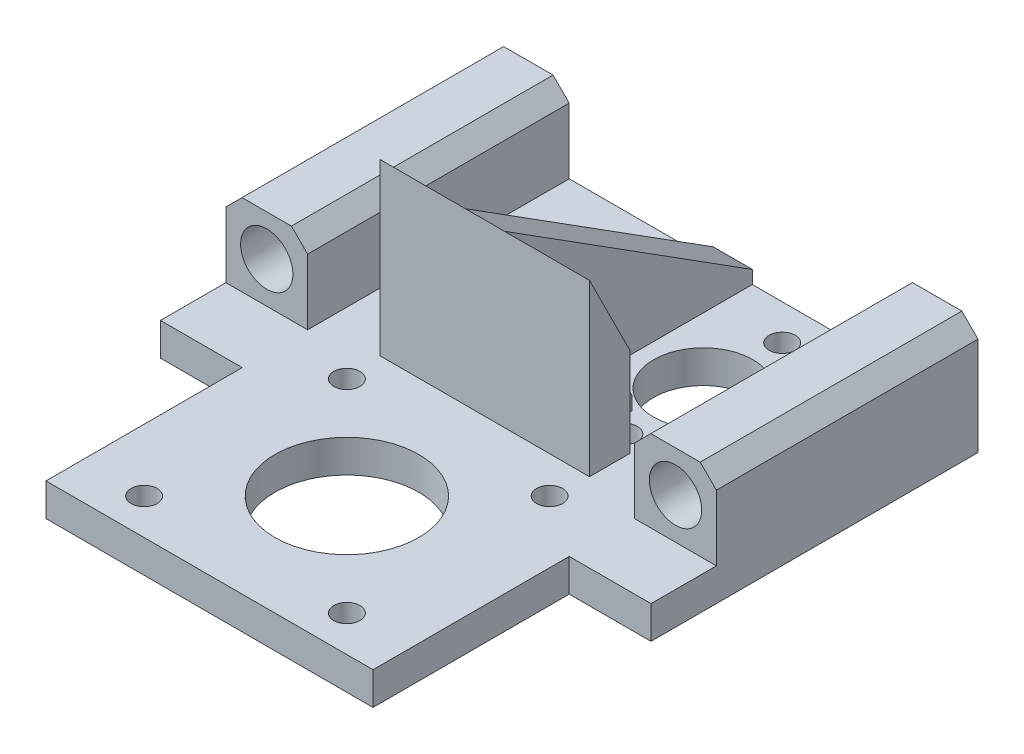
SolidWorks part; units mm, degrees
ref_plane "Front Plane" through (0, 0, 0) normal (0, 0, 1) x (1, 0, 0)
ref_plane "Top Plane" through (0, 0, 0) normal (0, 1, 0) x (1, 0, 0)
ref_plane "Right Plane" through (0, 0, 0) normal (1, 0, 0) x (0, 0, -1)
sketch "Sketch1" plane through (0, 0, 0) normal (0, 1, 0) x (1, 0, 0)
  line L0 (0, 32.5) -> (75, 32.5) construction
  line L1 (0, 0) -> (75, 0)
  line L2 (0, 0) -> (0, 50)
  line L3 (0, 50) -> (75, 50)
  line L4 (75, 0) -> (75, 50)
  line L5 (37.5, 50) -> (37.5, 0) construction
  line L6 (37.5, 32.5) -> (24.5, 32.5) construction
  line L7 (37.5, 32.5) -> (50.5, 32.5) construction
  circle A0 centre (24.5, 32.5) radius 5.1
  circle A1 centre (50.5, 32.5) radius 7.6
  point P15 (37.5, 32.5)
  dimension "D2" = 10.2
  dimension "D6" = 15.2
  dimension "D1" = 26
  dimension "D3" = 75
  dimension "D4" = 50
  dimension "D5" = 17.5
extrude "Boss-Extrude1" add sketch "Sketch1" along normal blind 5
sketch "Sketch2" plane through (0, 5, 0) normal (0, 1, 0) x (1, 0, 0)
  line L4 (0, 50) -> (12.5, 50)
  line L5 (0, 50) -> (0, 10)
  line L6 (0, 10) -> (12.5, 10)
  line L7 (12.5, 50) -> (12.5, 10)
  line L8 (75, 50) -> (62.5, 50)
  line L9 (75, 50) -> (75, 10)
  line L10 (75, 10) -> (62.5, 10)
  line L11 (62.5, 50) -> (62.5, 10)
  dimension "D1" = 40
  dimension "D3" = 12.5
extrude "Boss-Extrude2" add sketch "Sketch2" along normal blind 12.5
sketch "Sketch3" plane through (0, 0, -50) normal (0, 0, -1) x (-1, 0, 0)
  line L0 (-37.5, 0) -> (-37.5, 50000) construction
  line L1 (-75, 0) -> (0, 0) construction
  line L2 (-62.5, 5) -> (-12.5, 5) construction
  line L3 (-72.5251, 17.5) -> (-75, 17.5)
  line L4 (-75, 17.5) -> (-62.5, 17.5) construction
  line L5 (-75, 17.5) -> (-75, 15.0251)
  line L6 (-75, 17.5) -> (-75, 0) construction
  line L7 (-75, 15.0251) -> (-72.5251, 17.5)
  line L8 (-62.5, 17.5) -> (-64.9749, 17.5)
  line L9 (-64.9749, 17.5) -> (-62.5, 15.0251)
  line L10 (-62.5, 17.5) -> (-62.5, 5) construction
  line L11 (-62.5, 15.0251) -> (-62.5, 17.5)
  line L12 (-68.75, 17.5) -> (-68.75, 0) construction
  line L13 (-62.5, 11.25) -> (-75, 11.25) construction
  line L14 (-12.5, 11.25) -> (0, 11.25) construction
  line L15 (-6.25, 17.5) -> (-6.25, 0) construction
  line L16 (-12.5, 15.0251) -> (-12.5, 17.5)
  line L17 (-10.0251, 17.5) -> (-12.5, 15.0251)
  line L18 (-12.5, 17.5) -> (-10.0251, 17.5)
  line L19 (0, 15.0251) -> (-2.4749, 17.5)
  line L20 (0, 17.5) -> (0, 15.0251)
  line L21 (-2.4749, 17.5) -> (0, 17.5)
  circle A0 centre (-68.75, 11.25) radius 4
  circle A1 centre (-6.25, 11.25) radius 4
  point P4 (-37.5, 0)
  point P7 (-37.5, 5)
  dimension "D1" = 8
  dimension "D2" = 3.5
extrude "Cut-Extrude1" cut sketch "Sketch3" against normal through all
sketch "Sketch4" plane through (0, 5, 0) normal (0, 1, 0) x (1, 0, 0)
  line L0 (0, 0) -> (75, 0) construction
  line L1 (62.5, 0) -> (12.5, 0)
  line L2 (62.5, 0) -> (62.5, -30)
  line L3 (62.5, -30) -> (12.5, -30)
  line L4 (12.5, 0) -> (12.5, -30)
  line L5 (37.5, 50) -> (37.5, 0) construction
  line L6 (62.5, 50) -> (12.5, 50) construction
  point P10 (37.5, 0)
  dimension "D1" = 50
  dimension "D2" = 30
extrude "Boss-Extrude3" add sketch "Sketch4" against normal up to surface (5 mm away) up to face at (24.5, 0, -27.4)
sketch "Sketch5" plane through (0, 5, 0) normal (0, 1, 0) x (1, 0, 0)
  line L0 (37.5, -30) -> (37.5, 50) construction
  line L1 (12.5, -30) -> (62.5, -30) construction
  line L2 (62.5, 50) -> (12.5, 50) construction
  line L3 (58.5, -9) -> (16.5, -9) construction
  circle A0 centre (22, -24.5) radius 2
  circle A1 centre (22, 6.5) radius 2
  circle A2 centre (53, 6.5) radius 2
  circle A3 centre (53, -24.5) radius 2
  circle A4 centre (37.5, -9) radius 11
  point P8 (37.5, -9)
  dimension "D5" = 4
  dimension "D6" = 22
  dimension "D1" = 42
  dimension "D2" = 21
  dimension "D3" = 15.5
  dimension "D4" = 15.5
extrude "Cut-Extrude2" cut sketch "Sketch5" against normal through all
sketch "Sketch6" plane through (0, 5, 0) normal (0, 1, 0) x (1, 0, 0)
  line L0 (37.5, -30) -> (37.5, 12.1) construction
  line L1 (12.5, -30) -> (62.5, -30) construction
  line L3 (53.5, 12.1) -> (21.5, 12.1)
  line L4 (53.5, 12.1) -> (53.5, 24.1)
  line L5 (53.5, 24.1) -> (21.5, 24.1)
  line L6 (21.5, 12.1) -> (21.5, 24.1)
  point P9 (37.5, 12.1)
  dimension "D1" = 42.1
  dimension "D2" = 12
  dimension "D3" = 32
extrude "Boss-Extrude4" add sketch "Sketch6" along normal blind 2
sketch "Sketch8" plane through (53.5, 0, 0) normal (1, 0, 0) x (0, 0, -1)
  line L0 (24.1, 7) -> (12.1, 7)
  line L1 (12.1, 7) -> (12.1, 31)
  line L2 (12.1, 31) -> (24.1, 7)
  dimension "D1" = 24
extrude "Boss-Extrude6" add sketch "Sketch8" against normal up to surface (32 mm away) up to face at (21.5, 6, -18.1)
sketch "Sketch9" plane through (0, 5, 0) normal (0, 1, 0) x (1, 0, 0)
  line L0 (62.5, 50) -> (12.5, 50) construction
  line L1 (40.5, 50) -> (34.5, 50)
  line L2 (40.5, 50) -> (40.5, 24.1)
  line L3 (40.5, 24.1) -> (34.5, 24.1)
  line L4 (34.5, 50) -> (34.5, 24.1)
  line L5 (53.5, 24.1) -> (21.5, 24.1) construction
  line L6 (37.5, 50) -> (37.5, -138.6407) construction
  point P10 (37.5, 50)
  point P11 (37.5, 50)
  dimension "D1" = 6
extrude "Boss-Extrude7" add sketch "Sketch9" along normal up to vertex (2 mm away) up to point (21.5, 7, -24.1)
sketch "Sketch10" plane through (34.5, 0, 0) normal (-1, 0, 0) x (0, 0, 1)
  line L0 (-50, 7) -> (-12.1, 31)
  line L1 (-12.1, 31) -> (-24.1, 7)
  line L2 (-24.1, 7) -> (-50, 7)
  line L3 (-12.1, 31) -> (-24.1, 7) construction
extrude "Boss-Extrude8" add sketch "Sketch10" against normal up to surface (6 mm away) up to face at (40.5, 6, -37.05)
sketch "Sketch11" plane through (0, 5, 5) normal (0, 1, 0) x (1, 0, 0)
  line L0 (50.5, 29.9) -> (50.5, 45.1) construction
  line L1 (24.5, 42.6) -> (24.5, 32.4) construction
  line L2 (29.6, 37.5) -> (19.4, 37.5) construction
  line L3 (29.6, 37.5) -> (19.4, 37.5) construction
  line L5 (50.5, 29.9) -> (50.5, 45.1) construction
  circle A0 centre (50.5, 37.5) radius 7.6 construction
  circle A1 centre (50.5, 25.43) radius 2
  circle A2 centre (50.5, 49.565) radius 2
  circle A3 centre (24.5, 37.5) radius 5.1 construction
  circle A6 centre (24.5, 45.5) radius 1.5
  circle A7 centre (16.5, 37.5) radius 1.5
  circle A8 centre (32.5, 37.5) radius 1.5
  circle A9 centre (24.5, 29.5) radius 1.5
  point P5 (24.5, 37.5)
  point P10 (50.5, 37.5)
  point P20 (24.5, 37.5)
  dimension "D3" = 4
  dimension "D6" = 3
  dimension "D1" = 12.065
  dimension "D2" = 12.07
  dimension "D4" = 8
  dimension "D5" = 8
extrude "Cut-Extrude3" cut sketch "Sketch11" against normal through all both and the other way through all
sketch "Sketch13" plane through (0, 5, 0) normal (0, 1, 0) x (1, 0, 0)
  line L1 (53.5, 24.1) -> (48, 24.1)
  line L2 (53.5, 24.1) -> (53.5, 22.4258)
  line L3 (53.5, 22.4258) -> (48, 22.4258)
  line L4 (48, 24.1) -> (48, 22.4258)
  circle A0 centre (50.5, 20.43) radius 3.7
  circle A1 centre (24.5, 24.5) radius 2.75
  line M35 (53.5, 24.1) -> (53.5, 12.1)
  dimension "D1" = 5.5
  dimension "D2" = 7.4
  dimension "D3" = 5.5
  dimension "D4" = 1.6742
extrude "Cut-Extrude4" cut sketch "Sketch13" along normal through all contours A0 L2 M35 | A1 | A0 | L1 L4 L3 L2 region at (53.7824, 5, -20.43)
equation "\"8mm hole\" = 8mm"
equation "\"22mm hole\"= 22mm"
equation "\"D6@Sketch5\"= \"22mm hole\""
equation "\"D1@Sketch3\"= \"8mm hole\""
